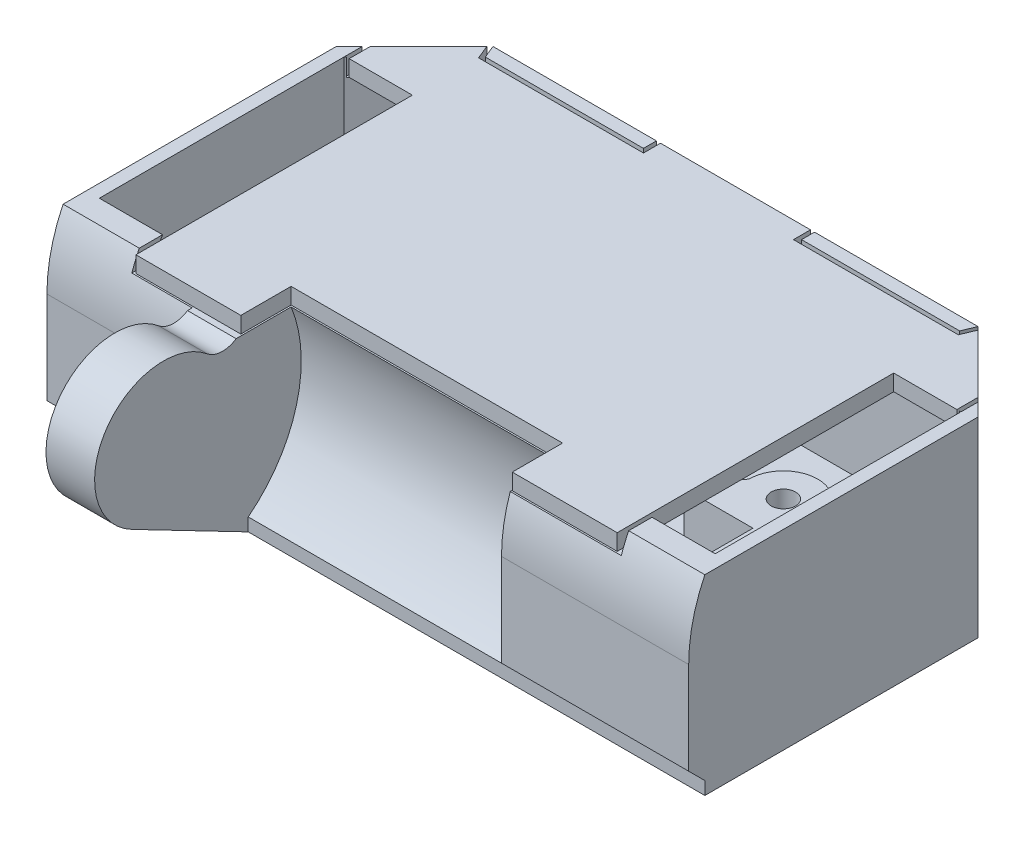
SolidWorks part; units mm, degrees
material "ABS PC"
ref_plane "Front Plane" through (0, 0, 0) normal (0, 0, 1) x (1, 0, 0)
ref_plane "Top Plane" through (0, 0, 0) normal (0, 1, 0) x (1, 0, 0)
ref_plane "Right Plane" through (0, 0, 0) normal (1, 0, 0) x (0, 0, -1)
sketch "Sketch1" plane through (0, 0, 0) normal (0, 1, 0) x (1, 0, 0)
  line L0 (0, -309.2525) -> (0, 15153.3717) construction
  line L1 (28.2, 1.5) -> (28.2, -1.5) construction
  line L2 (3, -6) -> (27, -6)
  line L3 (3, -6) -> (3, 6)
  line L4 (3, 6) -> (27, 6)
  line L5 (27, -6) -> (27, 6)
  line L6 (15, 6) -> (15, -6) construction
  line L7 (3, 0) -> (27, 0) construction
  line L8 (27.7, -2) -> (27, -2)
  line L9 (27.7, -2) -> (27.7, 2)
  line L10 (27.7, 2) -> (27, 2)
  line L11 (27, -2) -> (27, 2)
  line L12 (27.35, 2) -> (27.35, -2) construction
  line L13 (27.7, 0) -> (27, 0) construction
  line L14 (37, -1.5) -> (27.7, -1.5)
  line L15 (37, -1.5) -> (37, 1.5)
  line L16 (37, 1.5) -> (27.7, 1.5)
  line L17 (27.7, -1.5) -> (27.7, 1.5)
  line L18 (32.35, 1.5) -> (32.35, -1.5) construction
  line L19 (37, 0) -> (27.7, 0) construction
  line L20 (36.8, -16) -> (30.2, -16)
  line L21 (36.8, -16) -> (36.8, 16)
  line L22 (36.8, 16) -> (30.2, 16)
  line L23 (30.2, -16) -> (30.2, 16)
  line L24 (33.5, 16) -> (33.5, -16) construction
  line L25 (36.8, 0) -> (30.2, 0) construction
  line L26 (27, -7.5) -> (15.5, -7.5)
  line L27 (27, -7.5) -> (27, 7.5)
  line L28 (27, 7.5) -> (15.5, 7.5)
  line L29 (15.5, -7.5) -> (15.5, 7.5)
  line L30 (21.25, 7.5) -> (21.25, -7.5) construction
  line L31 (27, 0) -> (3, 0) construction
  line L32 (-27, 0) -> (-3, 0) construction
  line L33 (-21.25, 7.5) -> (-21.25, -7.5) construction
  line L34 (-36.8, 0) -> (-30.2, 0) construction
  line L35 (-33.5, 16) -> (-33.5, -16) construction
  line L36 (-37, 0) -> (-27.7, 0) construction
  line L37 (-32.35, 1.5) -> (-32.35, -1.5) construction
  line L38 (-27.7, 0) -> (-27, 0) construction
  line L39 (-27.35, 2) -> (-27.35, -2) construction
  line L40 (-3, 0) -> (-27, 0) construction
  line L41 (-15, 6) -> (-15, -6) construction
  line L42 (-28.2, 1.5) -> (-28.2, -1.5) construction
  line L43 (-15.5, -7.5) -> (-15.5, 7.5)
  line L44 (-27, 7.5) -> (-15.5, 7.5)
  line L45 (-27, -7.5) -> (-27, 7.5)
  line L46 (-27, -7.5) -> (-15.5, -7.5)
  line L47 (-30.2, -16) -> (-30.2, 16)
  line L48 (-36.8, 16) -> (-30.2, 16)
  line L49 (-36.8, -16) -> (-36.8, 16)
  line L50 (-36.8, -16) -> (-30.2, -16)
  line L51 (-27.7, -1.5) -> (-27.7, 1.5)
  line L52 (-37, 1.5) -> (-27.7, 1.5)
  line L53 (-37, -1.5) -> (-37, 1.5)
  line L54 (-37, -1.5) -> (-27.7, -1.5)
  line L55 (-27, -2) -> (-27, 2)
  line L56 (-27.7, 2) -> (-27, 2)
  line L57 (-27.7, -2) -> (-27.7, 2)
  line L58 (-27.7, -2) -> (-27, -2)
  line L59 (-27, -6) -> (-27, 6)
  line L60 (-3, 6) -> (-27, 6)
  line L61 (-3, -6) -> (-3, 6)
  line L62 (-3, -6) -> (-27, -6)
  line L63 (38, -995.0782) -> (38, 49004.9218) construction
  line L64 (-38, -995.0782) -> (-38, 49004.9218) construction
  line L65 (22.75, -9) -> (22.75, 9) construction
  line L66 (18.5, -9) -> (18.5, 9)
  line L67 (27, -9) -> (27, 9)
  line L68 (-22.75, -9) -> (-22.75, 9) construction
  line L69 (-18.5, -9) -> (-18.5, 9)
  line L70 (-27, -9) -> (-27, 9)
  circle A0 centre (22.75, 9) radius 1.5
  circle A1 centre (22.75, -9) radius 1.5
  circle A2 centre (-22.75, -9) radius 1.5
  circle A3 centre (-22.75, 9) radius 1.5
  arc A4 (18.5, -9) -> (27, -9) centre (22.75, -9) ccw
  arc A5 (27, 9) -> (18.5, 9) centre (22.75, 9) ccw
  arc A6 (-18.5, -9) -> (-27, -9) centre (-22.75, -9) cw
  arc A7 (-27, 9) -> (-18.5, 9) centre (-22.75, 9) cw
  point P1 (15, 0)
  point P7 (27.35, 0)
  point P12 (32.35, 0)
  point P16 (21.25, 0)
  point P17 (33.5, 0)
  point P77 (-33.5, 0)
  point P78 (-21.25, 0)
  point P79 (-32.35, 0)
  point P85 (-27.35, 0)
  point P86 (-15, 0)
  point P88 (38, 0)
  point P90 (22.75, 0)
  point P95 (-22.75, 0)
  point P100 (22.75, -13.25)
  point P104 (22.75, 13.25)
  point P106 (0, 0)
  point P107 (-22.75, 13.25)
  point P108 (-22.75, -13.25)
  dimension "D12" = 3
  dimension "D1" = 3
  dimension "D2" = 12
  dimension "D3" = 24
  dimension "D4" = 0.7
  dimension "D5" = 4
  dimension "D6" = 3
  dimension "D7" = 10
  dimension "D8" = 11.5
  dimension "D9" = 15
  dimension "D10" = 18
  dimension "D13" = 6.6
  dimension "D14" = 32
  dimension "D15" = 0.5
  dimension "D16" = 8.6
  dimension "D11" = 4.25
  dimension "D17" = 1
  dimension "D18" = 76
  dimension "D19" = 8.5
  dimension "D20" = 31
sketch "Sketch2" plane through (0, 0, 0) normal (0, 0, 1) x (1, 0, 0)
  line L0 (36.8, 0) -> (30.2, 0) construction
  line L1 (30.2, 32) -> (36.8, 32)
  line L2 (30.2, 32) -> (30.2, 0)
  line L3 (30.2, 0) -> (36.8, 0)
  line L4 (36.8, 32) -> (36.8, 0)
  line L5 (33.5, 0) -> (33.5, 32) construction
  line L6 (30.2, 16) -> (36.8, 16) construction
  line L7 (0, -1000) -> (0, 49000) construction
  line L8 (3, 0) -> (27, 0) construction
  line L9 (3, 11) -> (27, 11)
  line L10 (3, 11) -> (3, 21)
  line L11 (3, 21) -> (27, 21)
  line L12 (27, 11) -> (27, 21)
  line L13 (15, 21) -> (15, 11) construction
  line L14 (3, 16) -> (27, 16) construction
  line L15 (38, -960.9891) -> (38, 49039.0109) construction
  line L16 (15.5, 22.5) -> (27, 22.5)
  line L17 (15.5, 22.5) -> (15.5, 11)
  line L18 (15.5, 11) -> (27, 11)
  line L19 (27, 22.5) -> (27, 11)
  line L20 (21.25, 11) -> (21.25, 22.5) construction
  line L21 (15.5, 16.75) -> (27, 16.75) construction
  line L22 (-15.5, 16.75) -> (-27, 16.75) construction
  line L23 (-21.25, 11) -> (-21.25, 22.5) construction
  line L24 (-3, 16) -> (-27, 16) construction
  line L25 (-15, 21) -> (-15, 11) construction
  line L26 (-30.2, 16) -> (-36.8, 16) construction
  line L27 (-33.5, 0) -> (-33.5, 32) construction
  line L28 (-27, 22.5) -> (-27, 11)
  line L29 (-15.5, 11) -> (-27, 11)
  line L30 (-15.5, 22.5) -> (-15.5, 11)
  line L31 (-15.5, 22.5) -> (-27, 22.5)
  line L32 (-27, 11) -> (-27, 21)
  line L33 (-3, 21) -> (-27, 21)
  line L34 (-3, 11) -> (-3, 21)
  line L35 (-3, 11) -> (-27, 11)
  line L36 (-36.8, 32) -> (-36.8, 0)
  line L37 (-30.2, 0) -> (-36.8, 0)
  line L38 (-30.2, 32) -> (-30.2, 0)
  line L39 (-30.2, 32) -> (-36.8, 32)
  line L40 (-38, -960.9891) -> (-38, 49039.0109) construction
  point P0 (33.5, 16)
  point P4 (15, 16)
  point P12 (21.25, 16.75)
  point P42 (-21.25, 16.75)
  point P43 (-15, 16)
  point P44 (-33.5, 16)
  dimension "D1" = 32
  dimension "D2" = 10
  dimension "D3" = 11.5
sketch "Sketch3" plane through (0, 0, 0) normal (1, 0, 0) x (0, 0, -1)
  line L0 (34.1, 0) -> (-34.1, 0) construction
  line L1 (-1063.3991, 0) -> (48936.6009, 0) construction
  line L2 (-1069.8118, 11) -> (48930.1882, 11) construction
  line L4 (-1068.0845, 1) -> (48931.9155, 1) construction
  line L6 (-1000, 16) -> (49000, 16) construction
  line L7 (-1068.0845, 24.6) -> (48931.9155, 24.6) construction
  line L8 (-1063.3991, 32) -> (48936.6009, 32) construction
  line L9 (0, -984) -> (0, 49016) construction
  line L10 (-1013.3999, 22.6) -> (48986.6001, 22.6) construction
  line L11 (-1059.4795, 2.6) -> (48940.5205, 2.6) construction
  circle A0 centre (0, 16) radius 16
  circle A1 centre (-28, 16) radius 16
  circle A2 centre (-28, 16) radius 6.5
  circle A3 centre (-28, 16) radius 11
  circle A4 centre (-28, 16) radius 17 construction
  circle A5 centre (0, 16) radius 17 construction
  point P9 (-12, 16)
  point P10 (-16, 16)
  point P20 (-14.6642, 24.6)
  point P22 (0, 1)
  point P29 (0, 24.6)
  point P32 (0, 32)
  point P34 (0, 22.6)
  point P37 (0, 2.6)
  point P39 (-15.6665, 22.6)
  point P40 (-21.5, 16)
  point P41 (-17, 16)
  point P42 (14.6642, 24.6)
  point P46 (-17.5386, 2.6)
  point P47 (15.6665, 22.6)
  dimension "D1" = 13
  dimension "D3" = 22
  dimension "D2" = 6
  dimension "D4" = 2
  dimension "D5" = 1.6
  dimension "D6" = 20
  dimension "D7" = 20
  dimension "D9" = 1
  dimension "D8" = 1
  dimension "D10" = 1
ref_plane "Plane1" through (0, 11, 0) normal (0, 1, 0) x (1, 0, 0)
ref_plane "Plane2" through (0, 1, 0) normal (0, 1, 0) x (1, 0, 0)
sketch "Sketch4" plane through (0, 1, 0) normal (0, 1, 0) x (1, 0, 0)
  line L0 (-38, -200995.0782) -> (-38, 249004.9218) construction
  line L1 (39.6, 25.8404) -> (-39.6, 25.8404)
  line L2 (39.6, 25.8404) -> (39.6, -17.5386)
  line L3 (39.6, -17.5386) -> (-39.6, -17.5386)
  line L4 (-39.6, 25.8404) -> (-39.6, -17.5386)
  line L5 (0, -17.5386) -> (0, 25.8404) construction
  line L6 (39.6, 4.1509) -> (-39.6, 4.1509) construction
  line L7 (-38, 24.2404) -> (-39.6, 24.2404) construction
  line L8 (38, 24.2404) -> (-38, 24.2404) construction
  line L9 (38, 24.2404) -> (38, -17.5386) construction
  line L10 (38, -17.5386) -> (-38, -17.5386) construction
  line L11 (-38, 24.2404) -> (-38, -17.5386) construction
  line L12 (0, -17.5386) -> (0, 24.2404) construction
  line L13 (38, 3.3509) -> (-38, 3.3509) construction
  line L14 (-38, 24.2404) -> (-38, 25.8404) construction
  line L18 (-20, 22.2404) -> (20, 22.2404) construction
  line L19 (-20, 22.2404) -> (-20, 12.2404) construction
  line L20 (-20, 12.2404) -> (20, 12.2404) construction
  line L21 (20, 22.2404) -> (20, 12.2404) construction
  line L22 (0, 12.2404) -> (0, 22.2404) construction
  line L23 (-20, 17.2404) -> (20, 17.2404) construction
  arc A0 (27, 9) -> (18.5, 9) centre (22.75, 9) ccw construction
  point P0 (0, 4.1509)
  point P4 (0, 17.2404)
  point P8 (0, 3.3509)
  point P16 (20, 13.3033)
  dimension "D1" = 1.6
  dimension "D2" = 10
  dimension "D3" = 40
  dimension "D4" = 2
extrude "Boss-Extrude1" add sketch "Sketch4" along normal up to vertex (1.6 mm away) up to point (0, 2.6, 0)
sketch "Sketch5" plane through (0, 2.6, 0) normal (0, 1, 0) x (1, 0, 0)
  line L5 (27, -9) -> (27, 9) construction
  line L6 (27, -9) -> (27, 9)
  line L7 (0, -1000) -> (0, 49000) construction
  line L8 (18.5, 9) -> (17.375, 7.5)
  line L9 (27, 7.5) -> (15.5, 7.5) construction
  line L14 (17.375, 7.5) -> (15.5, 7.5)
  line L15 (15.5, 7.5) -> (15.5, -7.5)
  line L16 (15.5, -7.5) -> (17.375, -7.5)
  line L17 (27, -7.5) -> (15.5, -7.5) construction
  line L18 (17.375, -7.5) -> (18.5, -9)
  line L19 (-15.5, -7.5) -> (-17.375, -7.5)
  line L20 (-15.5, 7.5) -> (-15.5, -7.5)
  line L21 (-17.375, 7.5) -> (-15.5, 7.5)
  line L22 (-18.5, 9) -> (-17.375, 7.5)
  line L23 (-27, -9) -> (-27, 9)
  line L24 (-17.375, -7.5) -> (-18.5, -9)
  arc A3 (27, 9) -> (18.5, 9) centre (22.75, 9) ccw construction
  arc A4 (27, 9) -> (18.5, 9) centre (22.75, 9) ccw
  arc A5 (18.5, -9) -> (27, -9) centre (22.75, -9) ccw construction
  arc A6 (18.5, -9) -> (27, -9) centre (22.75, -9) ccw
  arc A7 (-27, 9) -> (-18.5, 9) centre (-22.75, 9) cw
  arc A8 (-18.5, -9) -> (-27, -9) centre (-22.75, -9) cw
extrude "Boss-Extrude2" add sketch "Sketch5" along normal up to surface (8.4 mm away) up to plane "Plane1"
sketch "Sketch15" plane through (0, 11, 0) normal (0, 1, 0) x (1, 0, 0)
  line L0 (-27, -7.5) -> (-27, 7.5) construction
  line L1 (24, -4) -> (-24, -4)
  line L2 (24, -4) -> (24, 4)
  line L3 (24, 4) -> (-24, 4)
  line L4 (-24, -4) -> (-24, 4)
  line L5 (0, 4) -> (0, -4) construction
  line L6 (24, 0) -> (-24, 0) construction
  line L7 (-3, -6) -> (-27, -6) construction
  point P0 (0, 0)
  dimension "D1" = 3
  dimension "D2" = 2
extrude "Cut-Extrude2" cut sketch "Sketch15" against normal up to surface (8.4 mm away) up to face at (19.5938, 2.6, 0)
sketch "Sketch6" plane through (0, 2.6, 0) normal (0, 1, 0) x (1, 0, 0)
  line L0 (0, -1000) -> (0, 49000) construction
  line L1 (38, -200995.0782) -> (38, 249004.9218) construction
  line L2 (29, -16) -> (38, -16)
  line L3 (29, -16) -> (29, 16)
  line L4 (29, 16) -> (38, 16)
  line L5 (38, -16) -> (38, 16)
  line L6 (33.5, 16) -> (33.5, -16) construction
  line L7 (29, 0) -> (38, 0) construction
  line L8 (36.8, 16) -> (30.2, 16) construction
  line L9 (-29, 0) -> (-38, 0) construction
  line L10 (-33.5, 16) -> (-33.5, -16) construction
  line L11 (-38, -16) -> (-38, 16)
  line L12 (-29, 16) -> (-38, 16)
  line L13 (-29, -16) -> (-29, 16)
  line L14 (-29, -16) -> (-38, -16)
  point P1 (33.5, 0)
  point P7 (0, 0)
  point P10 (0, 0)
  point P13 (0, 0)
  point P22 (-33.5, 0)
extrude "Cut-Extrude1" cut sketch "Sketch6" against normal through all
sketch "Sketch8" plane through (38, 0, 0) normal (-1, 0, 0) x (0, 0, 1)
  line L0 (10.6416, 2.6) -> (9.0416, 1)
  line L1 (9.0416, 1) -> (16, 1)
  line L2 (16, 1) -> (16, 2.6)
  line L3 (16, 2.6) -> (10.6416, 2.6)
  line L4 (0, -1000) -> (0, 49000) construction
  line L5 (-16, 2.6) -> (-10.6416, 2.6)
  line L6 (-16, 1) -> (-16, 2.6)
  line L7 (-9.0416, 1) -> (-16, 1)
  line L8 (-10.6416, 2.6) -> (-9.0416, 1)
  circle A1 centre (0, 16) radius 17 construction
  dimension "D1" = 45
extrude "Boss-Extrude3" add sketch "Sketch8" along normal up to surface (76 mm away) up to face at (-38, 1.8, 0)
ref_plane "Plane3" through (0, 32, 0) normal (0, 1, 0) x (1, 0, 0)
ref_plane "Plane4" through (0, 24.6, 0) normal (0, 1, 0) x (1, 0, 0)
sketch "Sketch10" plane through (0, 2.6, 0) normal (0, 1, 0) x (1, 0, 0)
  line L0 (-38, 24.2404) -> (-38, -17.5386)
  line L1 (-38, -17.5386) -> (-39.6, -17.5386)
  line L2 (-39.6, -17.5386) -> (-39.6, 25.8404)
  line L3 (-39.6, 25.8404) -> (39.6, 25.8404)
  line L4 (39.6, 25.8404) -> (39.6, -17.5386)
  line L5 (39.6, -17.5386) -> (38, -17.5386)
  line L6 (38, -17.5386) -> (38, 24.2404)
  line L7 (38, 24.2404) -> (-38, 24.2404)
  point P2 (0, 0)
  point P9 (0, 0)
  point P11 (0, 0)
  point P13 (0, 0)
  point P16 (0, 0)
  point P20 (0, 0)
extrude "Boss-Extrude4" add sketch "Sketch10" along normal up to vertex (22 mm away) up to point (0, 24.6, 0)
ref_plane "Plane6" through (-22.75, 0, 0) normal (1, 0, 0) x (0, 0, -1)
sketch "Sketch11" plane through (-22.75, 0, 0) normal (1, 0, 0) x (0, 0, -1)
  line L0 (-9, 11) -> (-13.25, 11)
  line L1 (-9, 11) -> (-9, 1)
  line L2 (-9, 1) -> (-17.5386, 1)
  line L4 (4, 11) -> (-4, 11) construction
  line L5 (-201000, 16) -> (249000, 16) construction
  line L6 (-17.5386, 1) -> (-31.9131, 8.4543)
  line L7 (-13.25, 11) -> (-21.32, 21.2561)
  arc A0 (-21.32, 21.2561) -> (-31.9131, 8.4543) centre (-28, 16) ccw
  circle A2 centre (-28, 16) radius 6.5 construction
  point P6 (0, 0)
  point P7 (-36.5, 16)
  point P13 (-34.5, 16)
  point P14 (-24.8342, 26.8342)
  point P18 (-24.8342, 26.8342)
  point P21 (-31.5728, 23.6625)
  point P22 (0, 0)
  point P23 (0, 0)
  point P24 (-17.2156, 19.2156)
  dimension "D2" = 2
extrude "Boss-Extrude5" add sketch "Sketch11" along normal blind 4
sketch "Sketch12" plane through (-38, 0, 0) normal (1, 0, 0) x (0, 0, -1)
  line L5 (-17.5386, 24.6) -> (24.2404, 24.6) construction
  line L6 (-17, 16) -> (-17, 2.6)
  line L7 (-17.5386, 2.6) -> (-10.6416, 2.6) construction
  line L8 (-17, 2.6) -> (-17.5386, 2.6)
  line L9 (-17.5386, 2.6) -> (-19.5337, 4.595)
  line L10 (-19.5337, 4.595) -> (-19.5337, 16)
  line L11 (-14.6642, 24.6) -> (-17.5386, 24.6)
  arc A2 (-14.6642, 24.6) -> (-17, 16) centre (0, 16) ccw
  circle A3 centre (0, 16) radius 17
  circle A4 centre (0, 16) radius 17 construction
  arc A5 (-17.5386, 24.6) -> (-19.5337, 16) centre (0, 16) ccw
  point P19 (-19.1145, 5.3611)
  dimension "D1" = 1
  dimension "D2" = 45
extrude "Boss-Extrude6" add sketch "Sketch12" along normal up to surface and the other way up to surface up to face at (-18.75, 9.2106, 18.6235) other way up to face at (-39.6, 12.8, -4.1509)
sketch "Sketch13" plane through (-18.75, 0, 0) normal (1, 0, 0) x (0, 0, -1)
  line L2 (-14.6642, 24.6) -> (24.2404, 24.6) construction
  line L5 (-10.4361, 2.6) -> (-17.5386, 2.6) construction
  line L6 (-13.3358, 24.6) -> (-11.5076, 24.6)
  line L7 (-15.1004, 2.6) -> (-17.5386, 2.6)
  arc A0 (-13.3358, 24.6) -> (-17.5386, 2.6) centre (-28, 16) cw
  arc A1 (-11.5076, 24.6) -> (-15.1004, 2.6) centre (-28, 16) cw
  arc A2 (-12.9263, 23.8602) -> (-16.21, 3.7527) centre (-28, 16) cw construction
  circle A3 centre (-28, 16) radius 17 construction
  dimension "D1" = 1.6
extrude "Boss-Extrude7" add sketch "Sketch13" along normal up to vertex (37.25 mm away) up to point (18.5, 0, 9)
sketch "Sketch14" plane through (-18.75, 0, 0) normal (1, 0, 0) x (0, 0, -1)
  line L0 (-13.3358, 24.6) -> (-14.6642, 24.6)
  line L8 (-17.5386, 1) -> (-17.5386, 2.6)
  line L9 (-11.7519, 11) -> (-13.25, 11)
  line L10 (-13.25, 11) -> (-17, 15.7659)
  line L11 (-17, 15.7659) -> (-17, 16)
  line L13 (-14.6642, 24.6) -> (-17.5386, 24.6)
  line L14 (-19.3405, 18.7404) -> (-21.32, 21.2561)
  line L15 (-31.9131, 8.4543) -> (-17.5386, 1)
  line L16 (-17.5386, 1) -> (-17.5386, 2.6)
  line L22 (-19.3405, 18.7404) -> (-21.32, 21.2561)
  line L23 (-31.9131, 8.4543) -> (-17.5386, 1)
  line L24 (-14.6642, 24.6) -> (-17.5386, 24.6)
  arc A2 (-17.5386, 2.6) -> (-11.7519, 11) centre (-28, 16) ccw
  arc A3 (-21.32, 21.2561) -> (-31.9131, 8.4543) centre (-28, 16) ccw
  arc A5 (-21.32, 21.2561) -> (-31.9131, 8.4543) centre (-28, 16) ccw
  arc A6 (-13.3358, 24.6) -> (-17.5386, 2.6) centre (-28, 16) cw
  circle A7 centre (-28, 16) radius 16 construction
  arc A12 (-14.6642, 24.6) -> (-17, 16) centre (0, 16) ccw
  arc A14 (-17.5386, 24.6) -> (-19.3405, 18.7404) centre (0, 16) ccw
  arc A15 (-17.5386, 24.6) -> (-19.3405, 18.7404) centre (0, 16) ccw
  point P15 (-13.7509, 23.6)
  dimension "D1" = 0
extrude "Boss-Extrude8" add sketch "Sketch14" along normal blind 2
sketch "Sketch19" plane through (38, 0, 0) normal (-1, 0, 0) x (0, 0, 1)
  line L5 (19.5337, 4.595) -> (19.5337, 16)
  line L6 (17.5386, 2.6) -> (19.5337, 4.595)
  line L7 (17, 2.6) -> (17.5386, 2.6)
  line L8 (17, 16) -> (17, 2.6)
  line L9 (17.5386, 24.6) -> (14.6642, 24.6)
  line L10 (19.5337, 4.595) -> (19.5337, 16)
  line L11 (17.5386, 2.6) -> (19.5337, 4.595)
  line L12 (17, 2.6) -> (17.5386, 2.6)
  line L13 (17, 16) -> (17, 2.6)
  line L14 (17.5386, 24.6) -> (14.6642, 24.6)
  arc A2 (17, 16) -> (14.6642, 24.6) centre (0, 16) ccw
  arc A3 (19.5337, 16) -> (17.5386, 24.6) centre (0, 16) ccw
  arc A4 (17, 16) -> (14.6642, 24.6) centre (0, 16) ccw
  arc A5 (19.5337, 16) -> (17.5386, 24.6) centre (0, 16) ccw
  dimension "D1" = 0
extrude "Boss-Extrude10" add sketch "Sketch19" along normal up to surface (19.5 mm away) and the other way up to surface (1.6 mm away) up to face at (18.5, 13.253, 12.4216) other way up to face at (39.6, 12.8, -4.1509)
sketch "Sketch20" plane through (18.5, 0, 0) normal (-1, 0, 0) x (0, 0, 1)
  line L0 (17.5386, 24.6) -> (14.6642, 24.6) construction
  line L1 (19.5337, 4.595) -> (19.5337, 16) construction
  line L2 (17.5386, 24.6) -> (14.6642, 24.6)
  line L3 (19.5337, 4.595) -> (19.5337, 16)
  line L4 (17.5386, 2.6) -> (19.5337, 4.595) construction
  line L5 (17.5386, 2.6) -> (19.5337, 4.595)
  line L7 (14.6642, 24.6) -> (13.3358, 24.6)
  arc A1 (19.5337, 16) -> (17.5386, 24.6) centre (0, 16) ccw construction
  arc A3 (19.5337, 16) -> (17.5386, 24.6) centre (0, 16) ccw
  arc A4 (13.3358, 24.6) -> (17.5386, 2.6) centre (28, 16) ccw
  circle A5 centre (28, 16) radius 16 construction
  point P10 (0, 0)
extrude "Boss-Extrude13" add sketch "Sketch20" along normal blind 2
fillet "Fillet1" radius 3 1 edges at (-19.75, 18.7404, 19.3405)
sketch "Sketch16" plane through (0, 2.6, 0) normal (0, 1, 0) x (1, 0, 0)
  line L0 (-39.6, 16.1698) -> (-29.9295, 25.8404)
  line L1 (-29.9295, 25.8404) -> (-27.6667, 25.8404)
  line L2 (-27.6667, 25.8404) -> (-39.6, 13.9071)
  line L3 (-39.6, 13.9071) -> (-39.6, 16.1698)
  line L4 (-34.7647, 21.0051) -> (-33.6334, 19.8737) construction
  line L5 (39.6, 25.8404) -> (-39.6, 25.8404) construction
  line L6 (-39.6, 25.8404) -> (-39.6, -17.5386) construction
  line L7 (-38, 24.2404) -> (-38, 25.8404) construction
  line L8 (0, -946.4498) -> (0, 47696.3752) construction
  line L10 (27.6667, 25.8404) -> (39.6, 13.9071)
  line L11 (29.9295, 25.8404) -> (27.6667, 25.8404)
  line L12 (39.6, 16.1698) -> (29.9295, 25.8404)
  line L13 (39.6, 13.9071) -> (39.6, 16.1698)
  dimension "D1" = 0.5
extrude "Boss-Extrude9" add sketch "Sketch16" along normal up to surface (22 mm away) up to face at (-0.0625, 24.6, 5.6432)
sketch "Sketch17" plane through (0, 1, 0) normal (0, -1, 0) x (1, 0, 0)
  line L0 (39.6, -16.1698) -> (29.9295, -25.8404) construction
  line L1 (-39.6, -16.1698) -> (-29.9295, -25.8404) construction
  line L2 (39.6, -16.1698) -> (29.9295, -25.8404)
  line L3 (-39.6, -16.1698) -> (-29.9295, -25.8404)
  line L4 (-39.6, -16.1698) -> (-39.6, -25.8404)
  line L5 (-39.6, -25.8404) -> (-29.9295, -25.8404)
  line L6 (29.9295, -25.8404) -> (39.6, -25.8404)
  line L7 (39.6, -25.8404) -> (39.6, -16.1698)
  point P6 (0, 0)
  point P9 (0, 0)
extrude "Cut-Extrude3" cut sketch "Sketch17" against normal through all
sketch "Sketch18" plane through (0, 1, 0) normal (0, -1, 0) x (1, 0, 0)
  circle A0 centre (-22.75, -9) radius 1.5
  circle A1 centre (-22.75, 9) radius 1.5
  circle A2 centre (22.75, 9) radius 1.5
  circle A3 centre (22.75, -9) radius 1.5
  circle A4 centre (22.75, -9) radius 1.5 construction
  circle A5 centre (22.75, 9) radius 1.5 construction
  circle A6 centre (-22.75, 9) radius 1.5 construction
  circle A7 centre (-22.75, -9) radius 1.5 construction
  dimension "D1" = 3
extrude "Cut-Extrude4" cut sketch "Sketch18" against normal through all
chamfer "Chamfer1" distance 2 angle 45 4 edges at (-22.75, 1, 7.5) (-22.75, 1, -10.5) (22.75, 1, -10.5) (22.75, 1, 7.5)
sketch "Sketch21" plane through (0, 24.6, 0) normal (0, 1, 0) x (1, 0, 0)
  line L0 (-30.2, -16) -> (-30.2, 16) construction
  line L3 (0, -19.5337) -> (-30.2, -19.5337)
  line L4 (-30.2, -19.5337) -> (-30.2, 15.6665)
  line L5 (-30.2, 15.6665) -> (-38, 15.6665)
  line L7 (0, -999.5952) -> (0, 48990.2839) construction
  line L10 (-38, 15.6665) -> (-38, 17.7698)
  line L11 (-38, 17.7698) -> (-29.9295, 25.8404)
  line L12 (-29.9295, 25.8404) -> (-29.2667, 24.2404)
  line L13 (38, 24.2404) -> (-38, 24.2404) construction
  line L14 (-27.6667, 25.8404) -> (-39.6, 13.9071) construction
  line L15 (29.9295, 25.8404) -> (29.2667, 24.2404)
  line L16 (38, 17.7698) -> (29.9295, 25.8404)
  line L17 (38, 15.6665) -> (38, 17.7698)
  line L18 (30.2, 15.6665) -> (38, 15.6665)
  line L19 (30.2, -19.5337) -> (30.2, 15.6665)
  line L20 (0, -19.5337) -> (30.2, -19.5337)
  line L21 (-29.2667, 24.2404) -> (-9.7556, 24.2404)
  line L22 (-9.7556, 24.2404) -> (-9.7556, 25.8404)
  line L23 (-9.7556, 25.8404) -> (9.7556, 25.8404)
  line L24 (9.7556, 25.8404) -> (9.7556, 24.2404)
  line L25 (9.7556, 24.2404) -> (29.2667, 24.2404)
  line L26 (39.6, 25.8404) -> (-39.6, 25.8404) construction
  line L27 (-38, -200995.0782) -> (-38, 249004.9218) construction
  line L28 (-39.6, 16.1698) -> (-29.9295, 25.8404) construction
  point P6 (-37.1966, 15.6665)
  point P35 (0, 0)
extrude "Cut-Extrude5" cut sketch "Sketch21" against normal blind 2.2
sketch "Sketch22" plane through (0, 24.6, 0) normal (0, 1, 0) x (1, 0, 0)
  line L0 (-37.5, -14.1642) -> (-29.7, -14.1642)
  line L1 (-35.1854, -14.1642) -> (-35.1854, -14.6642) construction
  line L2 (-37.5, -14.1642) -> (-38, -14.1642) construction
  line L3 (-38, -200995.0782) -> (-38, 249004.9218) construction
  line L4 (-37.5, -14.1642) -> (-37.5, 18.2698)
  line L5 (-37.5, 18.2698) -> (-30.3122, 25.4577)
  line L6 (-39.6, 16.1698) -> (-29.9295, 25.8404) construction
  line L7 (-30.3122, 25.4577) -> (-29.6008, 23.7404)
  line L8 (-29.6008, 23.7404) -> (-9.2556, 23.7404)
  line L9 (-29.9295, 25.8404) -> (-29.2667, 24.2404) construction
  line L10 (-29.2667, 24.2404) -> (-29.7287, 24.049) construction
  line L11 (-19.4282, 23.7404) -> (-19.4282, 24.2404) construction
  line L12 (-29.2667, 24.2404) -> (-9.7556, 24.2404) construction
  line L13 (-9.2556, 23.7404) -> (-9.2556, 25.8404)
  line L14 (39.6, 25.8404) -> (-39.6, 25.8404) construction
  line L15 (-9.7556, 24.2404) -> (-9.2556, 24.2404) construction
  line L16 (-29.7, -14.1642) -> (-29.7, -18.4555)
  line L17 (-30.2, -18.4555) -> (-22.75, -18.4555) construction
  line L18 (-29.7, -18.4555) -> (-30.2, -18.4555) construction
  line L19 (-30.2, -19.5337) -> (-30.2, 15.6665) construction
  line L20 (-29.7, -18.4555) -> (-16.75, -18.4555)
  line L21 (-16.75, -18.4555) -> (-16.75, -12.2507)
  line L22 (-16.75, -12.2507) -> (16.5, -12.2507) construction
  line L23 (-16.75, -19.0332) -> (-16.75, -12.2507) construction
  line L24 (0, -1000) -> (0, 49000) construction
  line L25 (16.75, -18.4555) -> (16.75, -12.2507)
  line L26 (29.7, -18.4555) -> (16.75, -18.4555)
  line L27 (29.7, -14.1642) -> (29.7, -18.4555)
  line L28 (37.5, -14.1642) -> (29.7, -14.1642)
  line L29 (37.5, -14.1642) -> (37.5, 18.2698)
  line L30 (37.5, 18.2698) -> (30.3122, 25.4577)
  line L31 (30.3122, 25.4577) -> (29.6008, 23.7404)
  line L32 (29.6008, 23.7404) -> (9.2556, 23.7404)
  line L33 (9.2556, 23.7404) -> (9.2556, 25.8404)
  line L34 (-16.75, -12.2507) -> (16.75, -12.2507)
  line L35 (-9.2556, 25.8404) -> (9.2556, 25.8404)
  dimension "D1" = 0.5
extrude "Boss-Extrude14" add sketch "Sketch22" against normal blind 2 separate body
sketch "Sketch24" plane through (0, 24.6, 0) normal (0, 1, 0) x (1, 0, 0)
  line L1 (-29.7, -15.6665) -> (-37.5, -15.6665)
  line L2 (-29.7, -15.6665) -> (-29.7, 15.6665)
  line L3 (-29.7, 15.6665) -> (-37.5, 15.6665)
  line L4 (-37.5, -15.6665) -> (-37.5, 15.6665)
  line L5 (-33.6, 15.6665) -> (-33.6, -15.6665) construction
  line L6 (-29.7, 0) -> (-37.5, 0) construction
  line L8 (29.7, -15.6665) -> (37.5, -15.6665)
  line L9 (29.7, -15.6665) -> (29.7, 15.6665)
  line L10 (29.7, 15.6665) -> (37.5, 15.6665)
  line L11 (37.5, -15.6665) -> (37.5, 15.6665)
  line L12 (33.6, 15.6665) -> (33.6, -15.6665) construction
  line L13 (29.7, 0) -> (37.5, 0) construction
  line L14 (29.7, -14.1642) -> (29.7, -18.4555) construction
  line L15 (37.5, -14.1642) -> (37.5, 18.2698) construction
  line L16 (3, 0) -> (27, 0) construction
  line L17 (-37.5, -14.1642) -> (-37.5, 18.2698) construction
  line L18 (-27, 0) -> (-3, 0) construction
  point P0 (-33.6, 0)
  point P4 (0, 0)
  point P5 (0, 0)
  point P8 (33.6, 0)
  point P12 (0, 0)
  point P13 (0, 0)
  point P16 (33.6, 1.9136)
  point P19 (0, 0)
  point P22 (0, 0)
extrude "Cut-Extrude8" cut sketch "Sketch24" against normal through all
equation "\"D1@Sketch2\"=\"D14@Sketch1\""
equation "\"D1@Boss-Extrude13\"=\"D1@Boss-Extrude8\""
